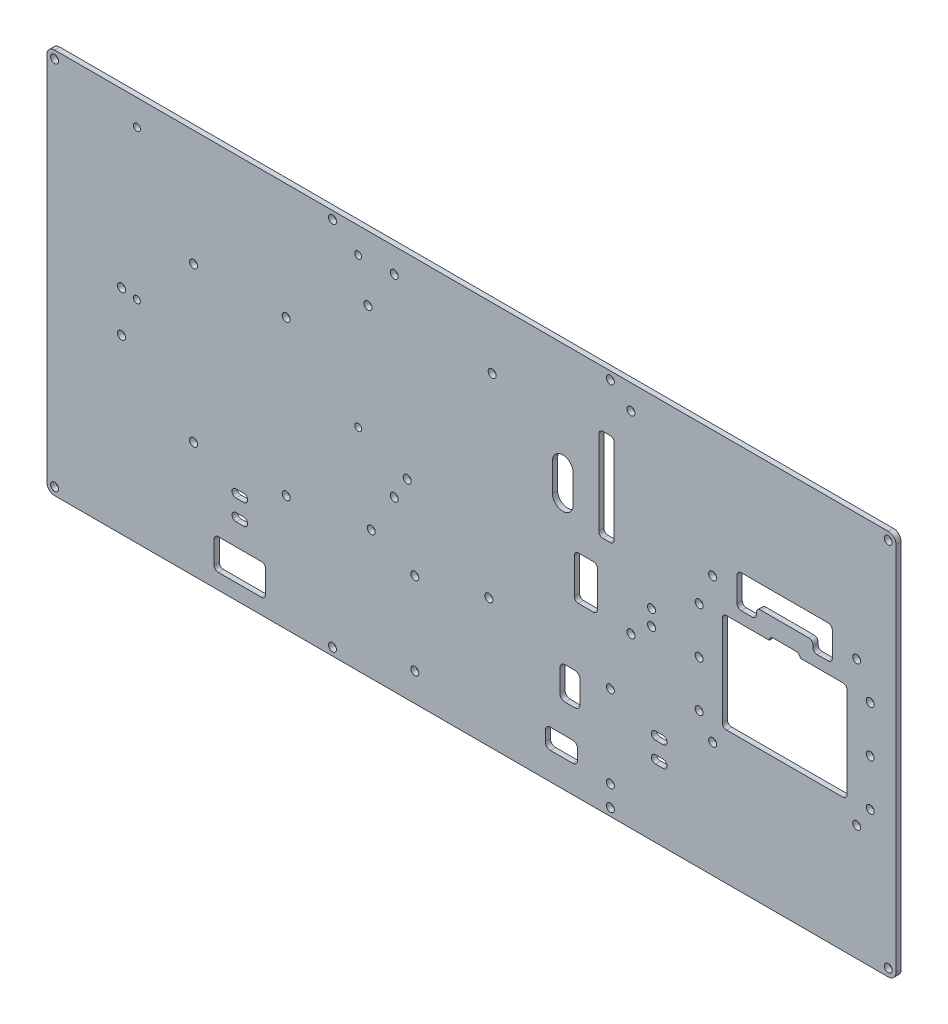
SolidWorks part; units mm, degrees
material "Thornel Mat VMA"
ref_plane "Front Plane" through (0, 0, 0) normal (0, 0, 1) x (1, 0, 0)
ref_plane "Top Plane" through (0, 0, 0) normal (0, 1, 0) x (1, 0, 0)
ref_plane "Right Plane" through (0, 0, 0) normal (1, 0, 0) x (0, 0, -1)
sketch "Sketch1" plane through (0, 0, 0) normal (0, 0, 1) x (1, 0, 0)
  line L0 (-165, 0) -> (165, 0) construction
  line L1 (165, -75) -> (-165, -75)
  line L2 (165, -75) -> (165, 75)
  line L3 (165, 75) -> (-165, 75)
  line L4 (-165, -75) -> (-165, 75)
  line L5 (165, -75) -> (-165, 75) construction
  line L6 (165, 75) -> (-165, -75) construction
  line L7 (0, -1.1) -> (0, 1.1) construction
  line L9 (70, -3) -> (70, 3)
  line L10 (-71, -3) -> (-71, 3) construction
  line L11 (121.75, 38.9) -> (121.75, -33.1) construction
  line L16 (157.75, -33.1) -> (85.75, -33.1) construction
  line L17 (157.75, -33.1) -> (157.75, 38.9) construction
  line L18 (157.75, 38.9) -> (85.75, 38.9) construction
  line L19 (85.75, -33.1) -> (85.75, 38.9) construction
  line L20 (157.75, -33.1) -> (85.75, 38.9) construction
  line L21 (157.75, 38.9) -> (85.75, -33.1) construction
  line L22 (97.5, 15.2) -> (146, 15.2)
  line L23 (97.5, 15.2) -> (97.5, -23.3)
  line L24 (97.5, -23.3) -> (146, -23.3)
  line L25 (146, 15.2) -> (146, -23.3)
  line L26 (97.5, 15.2) -> (146, -23.3) construction
  line L27 (97.5, -23.3) -> (146, 15.2) construction
  line L32 (103.25, 32.5) -> (140.25, 32.5)
  line L33 (103.25, 32.5) -> (103.25, 19.7)
  line L46 (103.25, 19.7) -> (140.25, 19.7)
  line L65 (165, -36) -> (165, 36)
  line L84 (140.25, 32.5) -> (140.25, 19.7)
  line L116 (103.25, 32.5) -> (140.25, 19.7) construction
  line L122 (-136, -8) -> (-136, 8)
  line L123 (16, 68.5) -> (16, -12.5) construction
  line L128 (-80, -69) -> (-100, -69)
  line L129 (-80, -69) -> (-80, -57)
  line L134 (-80, -57) -> (-100, -57)
  line L135 (-100, -69) -> (-100, -57)
  line L140 (-80, -69) -> (-100, -57) construction
  line L141 (-80, -57) -> (-100, -69) construction
  line L146 (-33, -12.5) -> (65, -12.5) construction
  line L147 (-33, -12.5) -> (-33, 68.5) construction
  line L175 (103.25, 19.7) -> (140.25, 32.5) construction
  line L176 (115.75, 16.7) -> (127.75, 16.7)
  line L177 (115.75, 16.7) -> (115.75, 15.2)
  line L178 (115.75, 15.2) -> (127.75, 15.2)
  line L179 (127.75, 16.7) -> (127.75, 15.2)
  line L180 (115.75, 16.7) -> (127.75, 15.2) construction
  line L181 (115.75, 15.2) -> (127.75, 16.7) construction
  line L182 (110.75, 23.7) -> (132.75, 23.7)
  line L183 (110.75, 23.7) -> (110.75, 19.7)
  line L184 (110.75, 19.7) -> (132.75, 19.7)
  line L185 (132.75, 23.7) -> (132.75, 19.7)
  line L186 (110.75, 23.7) -> (132.75, 19.7) construction
  line L187 (110.75, 19.7) -> (132.75, 23.7) construction
  line L188 (-33, 68.5) -> (65, 68.5) construction
  line L189 (65, -12.5) -> (65, 68.5) construction
  line L190 (-33, -12.5) -> (65, 68.5) construction
  line L191 (-33, 68.5) -> (65, -12.5) construction
  line L192 (-33, 28) -> (65, 28) construction
  line L193 (49, -9.5) -> (49, 7.5)
  line L201 (49, -9.5) -> (40, -9.5)
  line L202 (49, 7.5) -> (40, -9.5) construction
  line L207 (49, -9.5) -> (40, 7.5) construction
  line L208 (40, -9.5) -> (40, 7.5)
  line L212 (55.5, 17.2) -> (49.5, 17.2)
  line L213 (55.5, 17.2) -> (49.5, 53.2) construction
  line L214 (55.5, 53.2) -> (49.5, 17.2) construction
  line L215 (55.5, 53.2) -> (55.5, 17.2)
  line L216 (55.5, 53.2) -> (49.5, 53.2)
  line L217 (35.5, 22.5) -> (35.5, 33.5) construction
  line L218 (31.5, 22.5) -> (31.5, 33.5)
  line L219 (39.5, 22.5) -> (39.5, 33.5)
  line L220 (49.5, 53.2) -> (49.5, 17.2)
  line L221 (49, 7.5) -> (40, 7.5)
  circle A0 centre (-162, 72) radius 1.55
  circle A1 centre (-54, 72) radius 1.55
  circle A2 centre (-162, -72) radius 1.55
  circle A3 centre (-54, -72) radius 1.55
  circle A4 centre (162, -72) radius 1.55
  circle A5 centre (54, -72) radius 1.55
  circle A6 centre (162, 72) radius 1.55
  circle A7 centre (54, 72) radius 1.55
  circle A8 centre (-136, 0) radius 3.2 construction
  circle A15 centre (70, 3) radius 1.55
  circle A16 centre (70, -3) radius 1.55
  circle A75 centre (-71, 3) radius 1.55 construction
  circle A76 centre (-71, -3) radius 1.55 construction
  circle A83 centre (149.75, -30.1) radius 1.55
  circle A84 centre (155, -22.1) radius 1.55
  circle A85 centre (155, -4.1) radius 1.55
  circle A86 centre (155, 13.9) radius 1.55
  circle A87 centre (149.75, 25.9) radius 1.55
  circle A88 centre (93.75, -30.1) radius 1.55
  circle A89 centre (88.5, -22.1) radius 1.55
  circle A90 centre (88.5, -4.1) radius 1.55
  circle A91 centre (88.5, 13.9) radius 1.55
  circle A92 centre (93.75, 25.9) radius 1.55
  circle A95 centre (-136, 8) radius 1.55
  circle A96 centre (-136, -8) radius 1.55
  circle A101 centre (-30, 65.5) radius 1.55
  circle A102 centre (62, 65.5) radius 1.55
  circle A103 centre (-30, -9.5) radius 1.55
  circle A104 centre (62, -9.5) radius 1.55
  arc A109 (31.5, 22.5) -> (39.5, 22.5) centre (35.5, 22.5) ccw
  arc A110 (39.5, 33.5) -> (31.5, 33.5) centre (35.5, 33.5) ccw
  point P0 (0, 0)
  point P38 (70, 0)
  point P40 (0, 2.9)
  point P41 (-71, 0)
  point P42 (121.75, 2.9)
  point P47 (121.75, -4.05)
  point P52 (121.75, 26.1)
  point P58 (121.75, 21.7)
  point P62 (121.75, 15.95)
  point P78 (121.75, 19.7)
  point P120 (-76, -26.5)
  point P123 (-136, 0)
  point P141 (-90, -63)
  point P148 (16, 28)
  point P160 (35.5, 28)
  point P166 (52.5, 35.2)
  point P171 (44.5, -1)
  dimension "D5" = 3.1
  dimension "D8" = 94
  dimension "D18" = 37
  dimension "D31" = 28
  dimension "D10" = 3.1
  dimension "D47" = 3.1
  dimension "D57" = 3.1
  dimension "D80" = 3.1
  dimension "D1" = 150
  dimension "D2" = 330
  dimension "D3" = 3
  dimension "D4" = 3
  dimension "D6" = 108
  dimension "D7" = 29
  dimension "D9" = 6
  dimension "D11" = 10
  dimension "D12" = 90
  dimension "D13" = 6
  dimension "D14" = 72
  dimension "D15" = 72
  dimension "D16" = 38.5
  dimension "D17" = 48.5
  dimension "D19" = 12.8
  dimension "D20" = 1.5
  dimension "D21" = 12
  dimension "D22" = 9.8
  dimension "D23" = 22
  dimension "D24" = 4
  dimension "D25" = 4.5
  dimension "D30" = 3
  dimension "D33" = 4.05
  dimension "D45" = 81
  dimension "D48" = 5.25
  dimension "D49" = 8
  dimension "D50" = 18
  dimension "D51" = 70
  dimension "D56" = 16
  dimension "D58" = 98
  dimension "D59" = 20
  dimension "D60" = 12
  dimension "D61" = 63
  dimension "D63" = 46
  dimension "D64" = 37.5
  dimension "D70" = 18
  dimension "D71" = 56
  dimension "D72" = 7.2
  dimension "D73" = 36.5
  dimension "D76" = 28.5
  dimension "D77" = 29
  dimension "D78" = 54
  dimension "D79" = 28
extrude "Boss-Extrude1" add sketch "Sketch1" along normal blind 2 contours L2 L3 L4 L1 A16 A15 A8 A6 A5 A4 A2 A1 A0 | L2 | L185 L182 L183 L46 region at (-6.4359, -0.0408, 0) region at (121.75, 21.7, 0)
fillet "Fillet1" radius 3 4 edges at (165, 75, 1) (165, -75, 1) (-165, 75, 1) (-165, -75, 1)
fillet "Fillet2" radius 1.6 26 edges at (97.5, -23.3, 1) (146, -23.3, 1) (146, 15.2, 1) (127.75, 16.7, 1) (115.75, 16.7, 1) (97.5, 15.2, 1) (140.25, 32.5, 1) (103.25, 32.5, 1) (103.25, 19.7, 1) (110.75, 19.7, 1) (110.75, 23.7, 1) (132.75, 23.7, 1) (132.75, 19.7, 1) (140.25, 19.7, 1) (-100, -69, 1) (-80, -69, 1) (-80, -57, 1) (-100, -57, 1) (40, 7.5, 1) (49, 7.5, 1) (49, -9.5, 1) (40, -9.5, 1) (55.5, 17.2, 1) (49.5, 17.2, 1) (55.5, 53.2, 1) (49.5, 53.2, 1)
sketch "Sketch3" plane through (0, 0, 0) normal (0, 0, -1) x (-1, 0, 0)
  line L0 (55, 8.5) -> (55, -8.5) construction
  line L1 (60, 8.5) -> (60, -8.5)
  line L2 (50, 8.5) -> (50, -8.5)
  line L3 (165, -72) -> (165, 72) construction
  arc A0 (60, 8.5) -> (50, 8.5) centre (55, 8.5) ccw
  arc A1 (50, -8.5) -> (60, -8.5) centre (55, -8.5) ccw
  point P2 (55, 0)
  point P10 (165, 0)
  dimension "D1" = 10
  dimension "D2" = 17
  dimension "D3" = 110
extrude "Cut-Extrude1" [suppressed] cut sketch "Sketch3" against normal blind 3 contours L2 A1 L1 A0
sketch "Sketch4" plane through (0, 0, 2) normal (0, 0, 1) x (1, 0, 0)
  line L1 (-130, 65) -> (-44, 65) construction
  line L2 (-130, 65) -> (-130, 7) construction
  line L3 (-130, 7) -> (-44, 7) construction
  line L4 (-44, 65) -> (-44, 7) construction
  line L5 (-130, 65) -> (-44, 7) construction
  line L6 (-130, 7) -> (-44, 65) construction
  line L7 (-134, 69) -> (-34, 69) construction
  line L8 (-134, 69) -> (-134, -10) construction
  line L9 (-134, -10) -> (-34, -10) construction
  line L10 (-34, 69) -> (-34, -10) construction
  line L11 (-134, 69) -> (-34, -10) construction
  line L12 (-134, -10) -> (-34, 69) construction
  line L13 (165, 75) -> (-165, 75) construction
  circle A0 centre (-130, 65) radius 1.35
  circle A1 centre (-44, 65) radius 1.35
  circle A2 centre (-130, 7) radius 1.35
  circle A3 centre (-44, 7) radius 1.35
  point P13 (-87, 36)
  point P14 (-84, 29.5)
  dimension "D1" = 2.7
  dimension "D2" = 4
  dimension "D3" = 86
  dimension "D4" = 4
  dimension "D5" = 10
  dimension "D6" = 17
  dimension "D7" = 6
  dimension "D8" = 58
  dimension "D9" = 84
extrude "Jetson nano" cut sketch "Sketch4" against normal blind 10
sketch "Sketch5" plane through (0, 0, 2) normal (0, 0, 1) x (1, 0, 0)
  line L0 (-165, 0) -> (165, 0) construction
  line L1 (-68, 39) -> (-68, -39) construction
  line L2 (-68, 39) -> (-112, 39) construction
  line L3 (-112, 39) -> (-112, -39) construction
  line L4 (-68, -39) -> (-112, -39) construction
  line L5 (-68, 39) -> (-112, -39) construction
  line L6 (-112, 39) -> (-68, -39) construction
  line L7 (-72, 30) -> (-72, -30) construction
  line L8 (-72, 30) -> (-108, 30) construction
  line L9 (-108, 30) -> (-108, -30) construction
  line L10 (-72, -30) -> (-108, -30) construction
  line L11 (-72, 30) -> (-108, -30) construction
  line L12 (-108, 30) -> (-72, -30) construction
  line L13 (-38.9294, -25) -> (6.7906, -25) construction
  circle A0 centre (-108, -30) radius 1.55
  circle A1 centre (-108, 30) radius 1.55
  circle A2 centre (-72, -30) radius 1.55
  circle A3 centre (-72, 30) radius 1.55
  circle A4 centre (-38.9294, -25) radius 1.55
  circle A5 centre (6.7906, -25) radius 1.55
  circle A6 centre (-24.9594, -0.93) radius 1.55
  circle A7 centre (-40.1994, 49.87) radius 1.55
  circle A8 centre (8.0606, 51.17) radius 1.55
  point P0 (-90, 0)
  point P5 (-90, 0)
  point P31 (80, 0)
  dimension "D5" = 3.1
  dimension "D8" = 3.1
  dimension "D1" = 44
  dimension "D2" = 78
  dimension "D3" = 60
  dimension "D4" = 36
  dimension "D6" = 90
  dimension "D7" = 45.72
  dimension "D9" = 24.07
  dimension "D10" = 13.97
  dimension "D11" = 50.8
  dimension "D12" = 15.24
  dimension "D13" = 48.26
  dimension "D14" = 1.3
  dimension "D15" = 25
extrude "DCDC19V and MOAB" cut sketch "Sketch5" against normal blind 10
sketch "Sketch6" plane through (0, 0, 2) normal (0, 0, 1) x (1, 0, 0)
  line L0 (-22, -48) -> (54, -48) construction
  line L1 (-22, -32) -> (54, -32) construction
  line L2 (-22, -32) -> (-22, -64) construction
  line L3 (-22, -64) -> (54, -64) construction
  line L4 (54, -32) -> (54, -64) construction
  line L5 (16, -32) -> (16, -64) construction
  line L6 (162, -75) -> (-162, -75) construction
  line L7 (-25, -29) -> (57, -29) construction
  line L8 (-25, -29) -> (-25, -67) construction
  line L9 (-25, -67) -> (57, -67) construction
  line L10 (57, -29) -> (57, -67) construction
  line L11 (165, -72) -> (165, 72) construction
  line L12 (34.4, -32.7) -> (42.2, -32.7)
  line L13 (35.7, -34) -> (40.9, -34) construction
  line L14 (35.7, -34) -> (35.7, -44) construction
  line L15 (35.7, -44) -> (40.9, -44) construction
  line L16 (40.9, -34) -> (40.9, -44) construction
  line L17 (42.2, -32.7) -> (42.2, -45.3)
  line L18 (34.4, -45.3) -> (42.2, -45.3)
  line L19 (34.4, -32.7) -> (34.4, -45.3)
  line L20 (32, -60.5) -> (38, -60.5) construction
  line L21 (32, -58) -> (38, -58)
  line L22 (32, -63) -> (38, -63)
  line L24 (28.7, -56.6) -> (41.3, -56.6)
  line L25 (28.7, -56.6) -> (28.7, -64.4)
  line L26 (28.7, -64.4) -> (41.3, -64.4)
  line L27 (41.3, -56.6) -> (41.3, -64.4)
  line L28 (28.7, -56.6) -> (41.3, -64.4) construction
  line L29 (28.7, -64.4) -> (41.3, -56.6) construction
  circle A0 centre (54, -64) radius 1.55
  circle A1 centre (54, -32) radius 1.55
  circle A2 centre (-22, -64) radius 1.55
  circle A3 centre (-22, -32) radius 1.55
  arc A4 (32, -58) -> (32, -63) centre (32, -60.5) ccw
  arc A5 (38, -63) -> (38, -58) centre (38, -60.5) ccw
  point P30 (35, -60.5)
  point P35 (35, -60.5)
  dimension "D3" = 3.1
  dimension "D16" = 2.5
  dimension "D1" = 76
  dimension "D2" = 32
  dimension "D4" = 3
  dimension "D5" = 3
  dimension "D6" = 82
  dimension "D7" = 3
  dimension "D8" = 8
  dimension "D9" = 108
  dimension "D10" = 23
  dimension "D11" = 16.1
  dimension "D12" = 5.2
  dimension "D13" = 10
  dimension "D15" = 6
  dimension "D17" = 6.5
  dimension "D18" = 19
  dimension "D19" = 12.6
  dimension "D20" = 7.8
  dimension "D14" = 1.3
extrude "DCDC 5V10A case hole" cut sketch "Sketch6" against normal blind 10 contours L22 A5 L21 A4 | L27 L24 L25 L26 A5 L22 A4 L21 | L12 L19 L18 L17 | A1 | A0 | A2 | A3 region at (38.3, -39, 2) region at (35, -60.5, 2) region at (35, -56.7482, 2)
fillet "Fillet3" radius 2 8 edges at (42.2, -45.3, 1) (34.4, -45.3, 1) (34.4, -32.7, 1) (42.2, -32.7, 1) (41.3, -64.4, 1) (41.3, -56.6, 1) (28.7, -64.4, 1) (28.7, -56.6, 1)
sketch "Sketch7" plane through (0, 0, 2) normal (0, 0, 1) x (1, 0, 0)
  line L0 (-91.5, -39) -> (-88.5, -39) construction
  line L1 (-91.5, -37.45) -> (-88.5, -37.45)
  line L2 (-91.5, -40.55) -> (-88.5, -40.55)
  line L3 (-91.5, -47) -> (-88.5, -47) construction
  line L4 (-91.5, -45.45) -> (-88.5, -45.45)
  line L5 (-91.5, -48.55) -> (-88.5, -48.55)
  line L6 (-80, -67.4) -> (-80, -58.6) construction
  line L7 (-81.6, -57) -> (-98.4, -57) construction
  line L8 (0, 0) -> (0, -75) construction
  line L9 (162, -75) -> (-162, -75) construction
  line L10 (71.5, -39) -> (74.5, -39) construction
  line L13 (71.5, -37.45) -> (74.5, -37.45)
  line L16 (71.5, -40.55) -> (74.5, -40.55)
  line L17 (71.5, -47) -> (74.5, -47) construction
  line L18 (71.5, -45.45) -> (74.5, -45.45)
  line L19 (71.5, -48.55) -> (74.5, -48.55)
  arc A0 (-91.5, -37.45) -> (-91.5, -40.55) centre (-91.5, -39) ccw
  arc A1 (-88.5, -40.55) -> (-88.5, -37.45) centre (-88.5, -39) ccw
  arc A2 (-91.5, -45.45) -> (-91.5, -48.55) centre (-91.5, -47) ccw
  arc A3 (-88.5, -48.55) -> (-88.5, -45.45) centre (-88.5, -47) ccw
  arc A8 (71.5, -37.45) -> (71.5, -40.55) centre (71.5, -39) ccw
  arc A9 (74.5, -40.55) -> (74.5, -37.45) centre (74.5, -39) ccw
  arc A10 (71.5, -45.45) -> (71.5, -48.55) centre (71.5, -47) ccw
  arc A11 (74.5, -48.55) -> (74.5, -45.45) centre (74.5, -47) ccw
  point P2 (-90, -39)
  point P7 (-90, -47)
  point P16 (73, -39)
  point P30 (73, -47)
  dimension "D1" = 1.55
  dimension "D2" = 1.55
  dimension "D7" = 1.55
  dimension "D8" = 1.55
  dimension "D3" = 8
  dimension "D4" = 3
  dimension "D5" = 10
  dimension "D6" = 10
  dimension "D9" = 8
  dimension "D10" = 3
  dimension "D11" = 28
  dimension "D12" = 73
extrude "wiring tide hole" cut sketch "Sketch7" against normal blind 10
